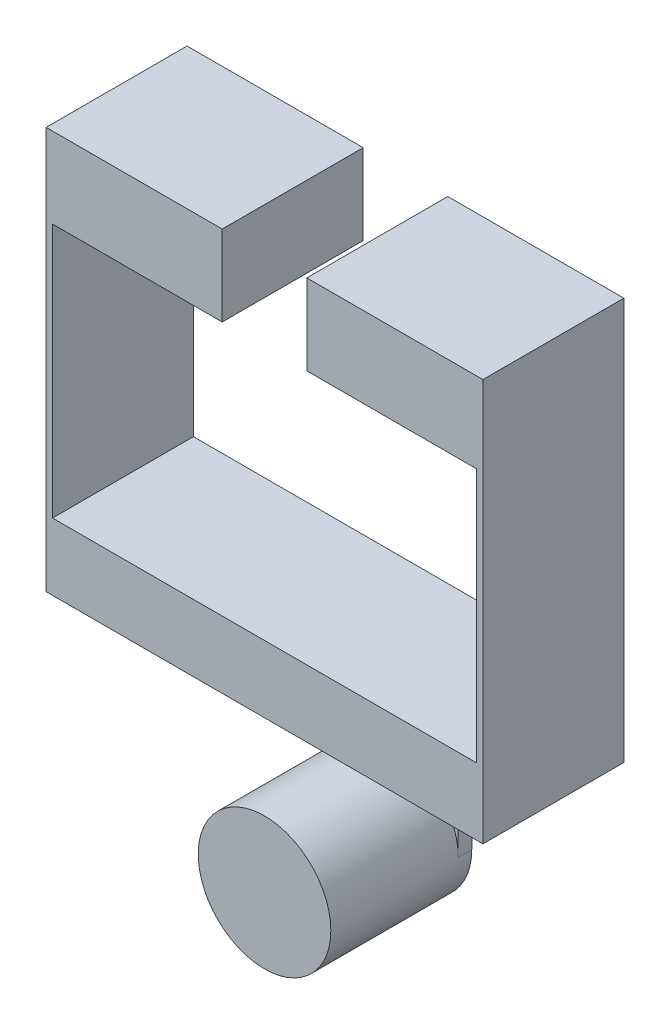
SolidWorks part; units mm, degrees
note: The reader was unsure of these and kept them because the rebuilt part matched: shared geometry of "Sketch6<3>".
ref_plane "Front Plane" through (0, 0, 0) normal (0, 0, 1) x (1, 0, 0)
ref_plane "Top Plane" through (0, 0, 0) normal (0, 1, 0) x (1, 0, 0)
ref_plane "Right Plane" through (0, 0, 0) normal (1, 0, 0) x (0, 0, -1)
sketch "Sketch1" plane through (0, 0, 0) normal (0, 0, 1) x (1, 0, 0)
  circle A0 centre (0, 0) radius 9.9132
  dimension "D1" = 19.8263
extrude "Boss-Extrude1" add sketch "Sketch1" along normal blind 21.0747
sketch "Sketch2" plane through (0, 0, 0) normal (0, 0, -1) x (-1, 0, 0)
  line L0 (-9.9132, 0) -> (9.9132, 0)
  line L1 (9.9132, 0) -> (9.9132, 22.6132)
  line L2 (9.9132, 22.6132) -> (-9.9132, 22.6132)
  line L3 (-9.9132, 22.6132) -> (-9.9132, 0)
  line L4 (0, 9.9132) -> (9.9132, 9.9132) construction
  circle A0 centre (0, 0) radius 9.9132 construction
extrude "Boss-Extrude2" add sketch "Sketch2" against normal blind 2.0247
sketch "Sketch3" plane through (0, 22.6132, 0) normal (0, 1, 0) x (1, 0, 0)
  line L0 (-9.9132, 0) -> (9.9132, 0) construction
  line L1 (-31.7043, 0) -> (31.7043, 0)
  line L2 (-31.7043, 0) -> (-31.7043, -21.0747)
  line L3 (-31.7043, -21.0747) -> (31.7043, -21.0747)
  line L4 (31.7043, 0) -> (31.7043, -21.0747)
  line L5 (-31.7043, 0) -> (31.7043, -21.0747) construction
  line L6 (-31.7043, -21.0747) -> (31.7043, 0) construction
  line L7 (0, -2.0247) -> (0, -78.8915) construction
  line L9 (-9.9132, -21.0747) -> (9.9132, -21.0747) construction
  point P0 (0, -10.5374)
  point P9 (0, 0)
  dimension "D1" = 63.4086
extrude "Boss-Extrude3" add sketch "Sketch3" along normal blind 10.014
sketch "Sketch4" plane through (0, 32.6272, 0) normal (0, 1, 0) x (1, 0, 0)
  line L0 (31.7043, 0) -> (32.6567, 0)
  line L3 (32.6567, 0) -> (32.6567, -21.0747)
  line L4 (32.6567, -21.0747) -> (31.7043, -21.0747)
  line L5 (-31.7043, -21.0747) -> (31.7043, -21.0747) construction
  line L6 (31.7043, -21.0747) -> (31.7043, 0) construction
  line M3 (31.7043, -21.0747) -> (31.7043, 0)
  dimension "D1" = 0.9524
extrude "Boss-Extrude4" add sketch "Sketch4" along normal blind 38.0746 contours L4 L3 L0 M3
sketch "Sketch5" plane through (0, 32.6272, 0) normal (0, -1, 0) x (1, 0, 0)
  line L4 (32.6567, 21.0747) -> (31.7043, 21.0747)
  line L5 (31.7043, 21.0747) -> (31.7043, 0)
  line L6 (31.7043, 0) -> (32.6567, 0)
  line L7 (32.6567, 0) -> (32.6567, 21.0747)
  line L8 (32.6567, 21.0747) -> (31.7043, 21.0747)
  line L9 (31.7043, 21.0747) -> (31.7043, 0)
  line L10 (31.7043, 0) -> (32.6567, 0)
  line L11 (32.6567, 0) -> (32.6567, 21.0747)
  dimension "D1" = 0
extrude "Boss-Extrude5" add sketch "Sketch5" along normal up to surface (10.014 mm away) up to face at (0, 22.6132, 5.7749)
sketch "Sketch6" plane through (31.7043, 0, 0) normal (-1, 0, 0) x (0, 0, 1)
  line L0 (0, 70.7018) -> (0, 82.7446)
  line L1 (0, 82.7446) -> (21.0747, 82.7446)
  line L2 (21.0747, 82.7446) -> (21.0747, 70.7018)
  line L3 (21.0747, 70.7018) -> (21.0747, 32.6272) construction
  line M4 (21.0747, 70.7018) -> (0, 70.7018)
  dimension "D1" = 12.0428
extrude "Boss-Extrude6" add sketch "Sketch6" along normal blind 25.3797 contours L2 L1 L0 M4
extrude "Boss-Extrude7" add sketch "Sketch6<3>" against normal up to surface (0.9524 mm away) contours L2 L1 L0 M4 up to face at (32.6567, 46.6575, 10.5374)
sketch "Sketch6<3>" plane through (31.7043, 0, 0) normal (-1, 0, 0) x (0, 0, 1) same geometry as "Sketch6"
mirror "Mirror4" about plane through (0, 0, 0) normal (1, 0, 0) of "Boss-Extrude5"
mirror "Mirror5" about plane through (0, 0, 0) normal (1, 0, 0) of "Boss-Extrude4"
mirror "Mirror8" about plane through (0, 0, 0) normal (1, 0, 0) of "Boss-Extrude5", "Boss-Extrude6", "Boss-Extrude7"
mirror "Mirror9" about plane through (0, 0, 0) normal (1, 0, 0) of "Boss-Extrude6"
sketch "Sketch7" plane through (0, 0, 21.0747) normal (0, 0, 1) x (1, 0, 0)
  line L0 (0, 32.693) -> (0, 89.7138) construction
  line L1 (0, 32.693) -> (-31.8318, 32.693)
  line L2 (-31.8318, 32.693) -> (-31.8318, 70.7676)
  line L3 (-31.8318, 70.7676) -> (-6.4522, 70.7676)
  line L4 (-6.4522, 70.7676) -> (-6.4522, 89.7138)
  line L5 (-6.4522, 89.7138) -> (0, 89.7138)
  line L6 (0, 89.7138) -> (6.197, 89.7138)
  line L7 (6.197, 89.7138) -> (6.197, 70.7676)
  line L8 (6.197, 70.7676) -> (31.5767, 70.7676)
  line L9 (31.5767, 70.7676) -> (31.5767, 32.693)
  line L10 (31.5767, 32.693) -> (0, 32.693)
  point P3 (-6.4522, 89.7138)
  dimension "D1" = 25.3797
  dimension "D2" = 25.3797
  dimension "D3" = 12.6492
  dimension "D4" = 38.0746
equation "\"T Rail Width Top\"= .498"
equation "\"T Rail Width lower\" = .9992"
equation "\"T Rail Thickness\"= 1.499"
equation "\"Strap Width\"= .75"
equation "\"W\" = 700"
equation "\"MAXO\"= 45 * 10 ^ 3"
equation "\"Saefty Factor\"= 4"
equation "\"Strap Frame Diameter\"= ( ( \"W\" * \"Strap Width\" * 32 ) / ( 3.14 * ( \"MAXO\" / \"Saefty Factor\" ) ) ) ^ ( 1 / 3 )"
equation "\"Member B\"= ( \"W\" / ( ( \"MAXO\" / 4 ) * \"Strap Frame Diameter\" ) )"
equation "\"Member B Length\"= 0.5"
equation "\"Member E Thickness\" = sqr ( ( ( \"W\" / 2 ) * ( \"T Rail Width lower\" ) * 6 ) / ( ( \"Member B\" + \"Strap Width\" ) * ( \"MAXO\" / \"Saefty Factor\" ) ) )"
equation "\"Member D Width\"= ( ( \"W\" / 2 ) / ( ( \"MAXO\" / \"Saefty Factor\" ) * ( \"Strap Width\" + \"Member B\" ) ) )"
equation "\"Feature C\"= sqr ( ( \"W\" * ( \"T Rail Width Top\" + 2 * \"T Rail Width lower\" ) * 6 ) / ( 4 * ( \"MAXO\" / \"Saefty Factor\" ) * \"T Rail Thickness\" ) )"
equation "\"D1@Sketch1\"=\"Strap Frame Diameter\""
equation "\"D1@Boss-Extrude1\"=\"Strap Width\" + \"Member B\""
equation "\"D1@Sketch2\"=\"Member B Length\""
equation "\"D1@Boss-Extrude2\"=\"Member B\""
equation "\"D1@Sketch3\"=\"T Rail Width Top\" + \"T Rail Width lower\" * 2"
equation "\"D1@Boss-Extrude3\"=\"Feature C\""
equation "\"D1@Sketch4\"=\"Member D Width\""
equation "\"D1@Boss-Extrude4\"=\"T Rail Thickness\""
equation "\"D1@Sketch6\"=\"Member E Thickness\""
equation "\"D1@Boss-Extrude6\"=\"T Rail Width lower\""
equation "\"D1@Sketch7\"=\"T Rail Width lower\""
equation "\"D2@Sketch7\"=\"T Rail Width lower\""
equation "\"D3@Sketch7\"=\"T Rail Width Top\""
equation "\"D4@Sketch7\"=\"T Rail Thickness\""
